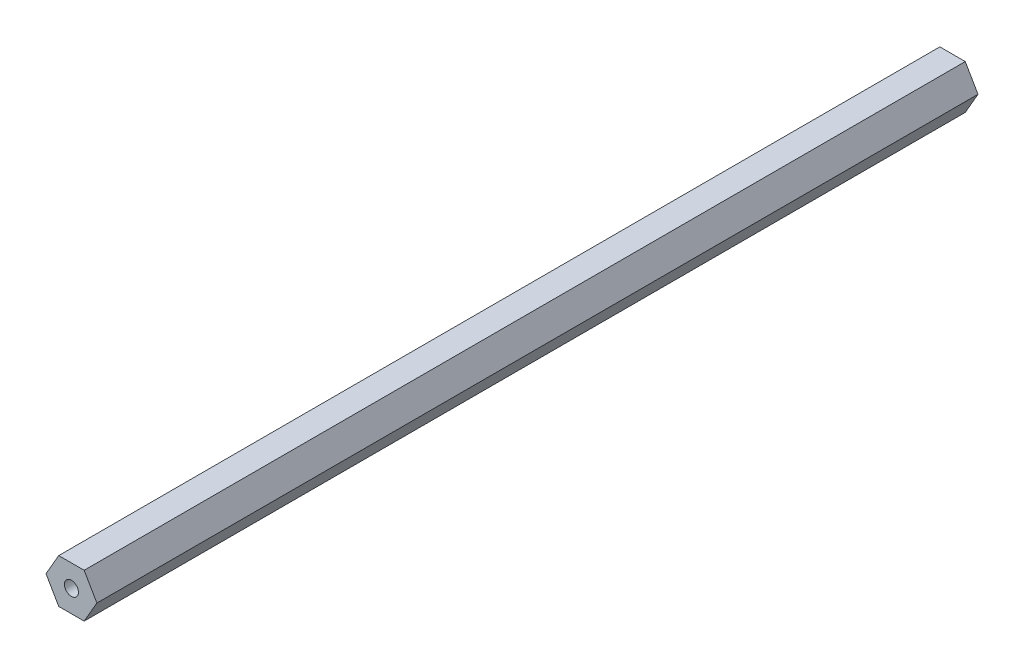
SolidWorks part; units mm, degrees
material "6061-T6 (SS)"
ref_plane "Front" through (0, 0, 0) normal (0, 0, 1) x (1, 0, 0)
ref_plane "Top" through (0, 0, 0) normal (0, 1, 0) x (1, 0, 0)
ref_plane "Right" through (0, 0, 0) normal (1, 0, 0) x (0, 0, -1)
sketch "Sketch1" plane through (0, 0, 0) normal (0, 0, 1) x (1, 0, 0)
  line L1 (7.3323, 0) -> (3.6662, 6.35)
  line L2 (3.6662, 6.35) -> (-3.6662, 6.35)
  line L3 (-3.6662, 6.35) -> (-7.3323, 0)
  line L4 (-7.3323, 0) -> (-3.6662, -6.35)
  line L5 (-3.6662, -6.35) -> (3.6662, -6.35)
  line L6 (3.6662, -6.35) -> (7.3323, 0)
  circle A0 centre (0, 0) radius 6.35 construction
  dimension "D1" = 12.7
extrude "Boss-Extrude1" add sketch "Sketch1" along normal blind 254
hole_wizard "#10-32 Tapped Hole1" positions "Sketch2" profile "Sketch4" tap size "#10-32" standard "ANSI Inch"
sketch "Sketch2" plane through (0, 0, 254) normal (0, 0, 1) x (1, 0, 0)
  point P0 (0, 0)
sketch "Sketch4" plane through (0, 0, 254) normal (1, 0, 0) x (0, -1, 0)
  line L0 (0, 0) -> (0, 77.4133)
  line L1 (0, 77.4133) -> (2.0193, 76.2)
  line L2 (2.0193, 76.2) -> (2.0193, 0)
  line L5 (2.0193, 0) -> (0, 0)
  line L10 (0, 77.4133) -> (-2.0193, 76.2) construction
  line L11 (0, -6.35) -> (0, 107.95) construction
  dimension "Tap Drill Dia." = 4.0386
  dimension "Tap Drill Depth" = 76.2
  dimension "Drill Angle" = 118
cosmetic thread "Hole Thread1" parameters "D1"=9.652, "D2"=4.826
